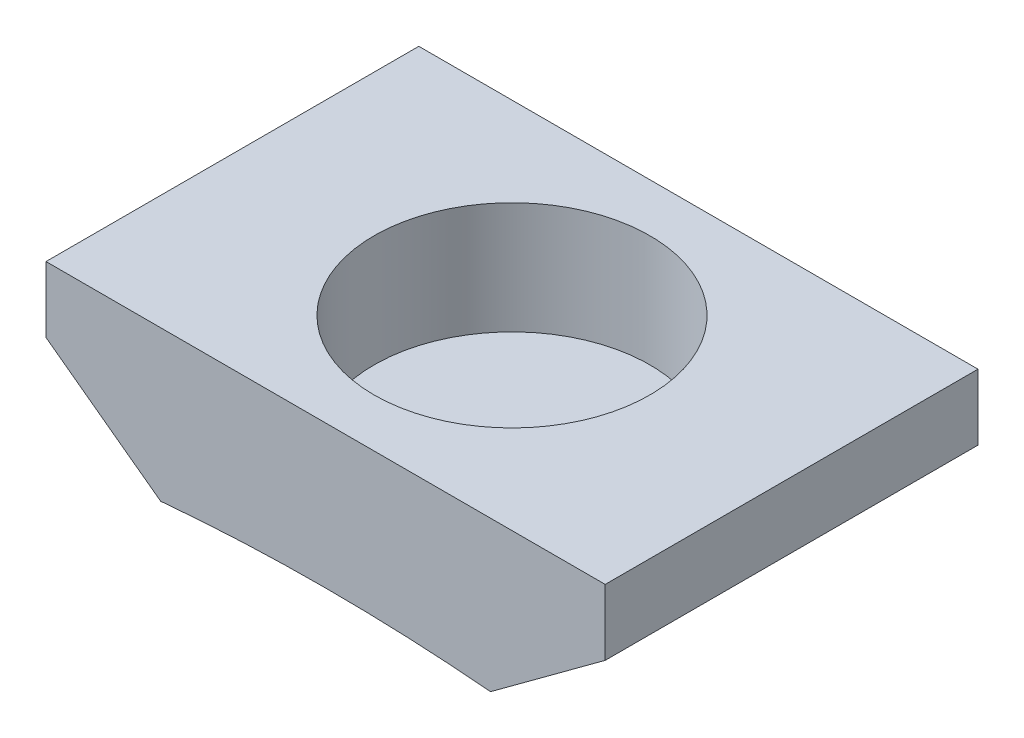
SolidWorks part; units mm, degrees
ref_plane "Спереди" through (0, 0, 0) normal (0, 0, 1) x (1, 0, 0)
ref_plane "Сверху" through (0, 0, 0) normal (0, 1, 0) x (1, 0, 0)
ref_plane "Справа" through (0, 0, 0) normal (1, 0, 0) x (0, 0, -1)
sketch "Sketch1" plane through (0, 0, 0) normal (0, 1, 0) x (1, 0, 0)
  line L1 (7.5, -5) -> (-7.5, -5)
  line L2 (7.5, -5) -> (7.5, 5)
  line L3 (7.5, 5) -> (-7.5, 5)
  line L4 (-7.5, -5) -> (-7.5, 5)
  line L5 (7.5, -5) -> (-7.5, 5) construction
  line L6 (7.5, 5) -> (-7.5, -5) construction
  point P0 (0, 0)
  dimension "D1" = 10
  dimension "D2" = 15
extrude "Boss-Extrude1" add sketch "Sketch1" along normal blind 1.4
sketch "Sketch2" plane through (0, 1.4, 0) normal (0, 1, 0) x (1, 0, 0)
  line L0 (0, -5) -> (0, 5) construction
  line L1 (-7.5, -5) -> (7.5, -5) construction
  line L2 (7.5, 5) -> (-7.5, 5) construction
  line L4 (7.5, -5) -> (-7.5, -5)
  line L5 (7.5, -5) -> (7.5, 5)
  line L6 (7.5, 5) -> (-7.5, 5)
  line L7 (-7.5, -5) -> (-7.5, 5)
  line L8 (7.5, -5) -> (-7.5, 5) construction
  line L9 (7.5, 5) -> (-7.5, -5) construction
  circle A0 centre (0, 0) radius 3.7
  point P6 (0, 0)
  dimension "D1" = 7.4
extrude "Boss-Extrude2" add sketch "Sketch2" along normal blind 3
sketch "Sketch5" plane through (0, 0, -5) normal (0, 0, -1) x (-1, 0, 0)
  line L0 (7.5, 0) -> (-7.5, 0)
  arc A0 (7.5, 0) -> (-7.5, 0) centre (0, -49.4343) ccw
  dimension "D1" = 50
extrude "Cut-Extrude2" cut sketch "Sketch5" against normal through all
chamfer "Chamfer1" distance 3 angle 45 2 edges at (7.5, 0, 0) (-7.5, 0, 0) first distance on face at (0, 0.2829, 0)
